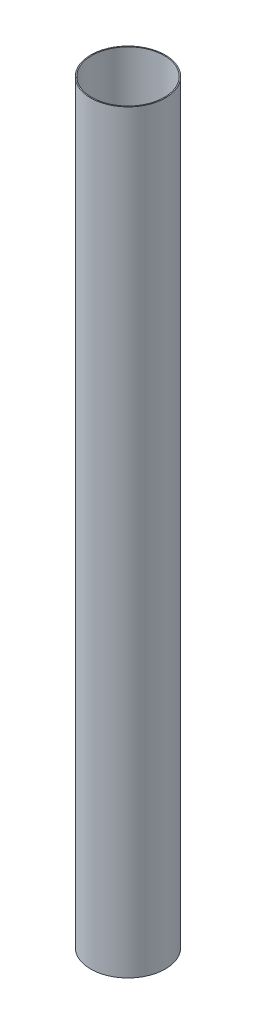
SolidWorks part; units mm, degrees
material "Thornel Mat VMA"
ref_plane "Front Plane" through (0, 0, 0) normal (0, 0, 1) x (1, 0, 0)
ref_plane "Top Plane" through (0, 0, 0) normal (0, 1, 0) x (1, 0, 0)
ref_plane "Right Plane" through (0, 0, 0) normal (1, 0, 0) x (0, 0, -1)
sketch "Sketch1" plane through (0, 0, 0) normal (0, 1, 0) x (1, 0, 0)
  circle A0 centre (0, 0) radius 46.1137
  circle A1 centre (0, 0) radius 44.8437
  dimension "D1" = 92.2274
  dimension "D2" = 1.27
extrude "Extrude1" add sketch "Sketch1" along normal blind 932.6267
